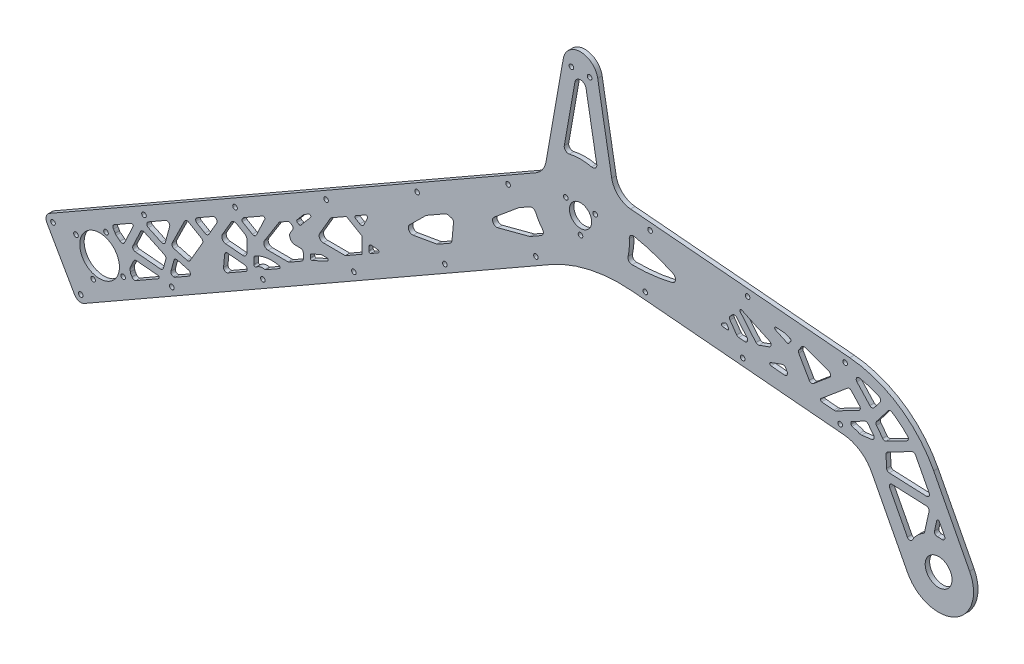
SolidWorks part; units mm, degrees
material "6061-T6 (SS)"
ref_plane "Front Plane" through (0, 0, 0) normal (0, 0, 1) x (1, 0, 0)
ref_plane "Top Plane" through (0, 0, 0) normal (0, 1, 0) x (1, 0, 0)
ref_plane "Right Plane" through (0, 0, 0) normal (1, 0, 0) x (0, 0, -1)
sketch "Reference Sketch" plane through (0, 0, 0) normal (0, 0, 1) x (1, 0, 0)
  line L0 (-343.92, -196.825) -> (0, 0) construction
  line L1 (-243.92, 103.175) -> (356.08, 103.175) construction
  line L2 (-243.92, 103.175) -> (-243.92, 0) construction
  line L3 (-243.92, 0) -> (356.08, 0) construction
  line L4 (356.08, 103.175) -> (356.08, 0) construction
  line L5 (0, 0) -> (256.08, -92.7116) construction
  line L6 (256.08, -92.7116) -> (56.08, -196.825) construction
  line L7 (256.08, -92.7116) -> (456.08, -196.825) construction
  line L8 (-343.92, -196.825) -> (56.08, -196.825) construction
  line L9 (56.08, -196.825) -> (456.08, -196.825) construction
  circle A1 centre (-343.92, -196.825) radius 100 construction
  circle A2 centre (56.08, -196.825) radius 100 construction
  circle A3 centre (456.08, -196.825) radius 100 construction
  circle A4 centre (-343.92, -196.825) radius 16.05 construction
  circle A5 centre (-343.92, -196.825) radius 28.55 construction
  circle A6 centre (-343.92, -196.825) radius 38.55 construction
  circle A7 centre (-343.92, -196.825) radius 33.55 construction
  point P13 (-343.92, -296.825)
  point P14 (556.08, -196.825)
  point P17 (-443.92, -196.825)
  dimension "D3" = 32.1
  dimension "D5" = 200
  dimension "D9" = 57.1
  dimension "D10" = 10
  dimension "D11" = 5
  dimension "D1" = 600
  dimension "D2" = 103.175
  dimension "D4" = 243.92
  dimension "D6" = 125
  dimension "D7" = 400
  dimension "D8" = 1000
  dimension "D12" = 356.08
sketch "Sketch2" plane through (0, 0, 0) normal (0, 0, 1) x (1, 0, 0)
  line L0 (-379.7168, -188.5069) -> (-32.0065, 10.4873)
  line L1 (-354.8814, -231.9028) -> (-21.5627, -41.1449)
  line L2 (-343.92, -196.825) -> (0, 0) construction
  line L3 (-184.3777, -76.7146) -> (-159.5423, -120.1104) construction
  line L4 (-24.685, 20.9013) -> (-12.3101, 91.0831)
  line L5 (12.3101, 91.0831) -> (22.322, 34.3028)
  line L6 (0, 98.4125) -> (0, 112.7) construction
  line L7 (-5.4848, 79.4125) -> (5.4848, 79.4125) construction
  line L8 (5.4848, 79.4125) -> (10.9697, 88.9125) construction
  line L9 (10.9697, 88.9125) -> (5.4848, 98.4125) construction
  line L10 (5.4848, 98.4125) -> (-5.4848, 98.4125) construction
  line L11 (-5.4848, 98.4125) -> (-10.9697, 88.9125) construction
  line L12 (-10.9697, 88.9125) -> (-5.4848, 79.4125) construction
  line L13 (-243.92, 103.175) -> (356.08, 103.175) construction
  line L14 (0, 88.9125) -> (0, 0) construction
  line L15 (35.7868, 21.9646) -> (192.5861, 8.2464)
  line L16 (252.5753, -31.8371) -> (278.2553, -81.1679)
  line L17 (233.9047, -104.2553) -> (208.2247, -54.9245)
  line L18 (36.8237, -28.3172) -> (188.2284, -41.5633)
  line L19 (0, 0) -> (192.5861, -16.8491) construction
  line L21 (-360.8064, -192.2315) -> (-339.3265, -179.9386) construction
  line L22 (-381.5729, -195.33) -> (-361.7045, -230.0467)
  line L23 (256.08, -92.7116) -> (56.08, -196.825) construction
  line L25 (-243.92, 0) -> (356.08, 0) construction
  circle A0 centre (0, 0) radius 7.9375
  circle A1 centre (-343.92, -196.825) radius 14.2
  arc A3 (-12.3101, 91.0831) -> (12.3101, 91.0831) centre (0, 88.9125) cw
  circle A4 centre (0, 88.9125) radius 6.5 construction
  circle A5 centre (-6.5, 88.9125) radius 1.65
  circle A6 centre (6.5, 88.9125) radius 1.65
  circle A7 centre (0, 88.9125) radius 9.5 construction
  arc A8 (252.5753, -31.8371) -> (192.5861, 8.2464) centre (186.0495, -66.4682) ccw
  circle A9 centre (256.08, -92.7116) radius 9.5885
  arc A10 (278.2553, -81.1679) -> (233.9047, -104.2553) centre (256.08, -92.7116) cw
  arc A11 (-21.5627, -41.1449) -> (36.8237, -28.3172) centre (28.1082, -127.9366) cw
  arc A12 (188.2284, -41.5633) -> (208.2247, -54.9245) centre (186.0495, -66.4682) cw
  arc A13 (22.322, 34.3028) -> (35.7868, 21.9646) centre (37.0941, 36.9075) ccw
  arc A14 (-32.0065, 10.4873) -> (-24.685, 20.9013) centre (-39.4572, 23.506) ccw
  circle A17 centre (-343.92, -196.825) radius 17.5 construction
  circle A18 centre (-360.8064, -192.2315) radius 1.65
  circle A19 centre (-339.3265, -179.9386) radius 1.65
  circle A20 centre (-327.0336, -201.4185) radius 1.65
  circle A21 centre (-348.5135, -213.7114) radius 1.65
  arc A27 (-379.7168, -188.5069) -> (-381.5729, -195.33) centre (-377.2333, -192.8465) ccw
  arc A28 (-361.7045, -230.0467) -> (-354.8814, -231.9028) centre (-357.3649, -227.5632) ccw
  circle A29 centre (-343.92, -196.825) radius 33.55 construction
  circle A32 centre (-343.92, -196.825) radius 38.55 construction
  point P16 (-171.96, -98.4125)
  point P64 (-343.92, -196.825)
  dimension "D1" = 15.875
  dimension "D2" = 28.4
  dimension "D3" = 35
  dimension "D5" = 13
  dimension "D6" = 3.3
  dimension "D7" = 6
  dimension "D12" = 50
  dimension "D14" = 100
  dimension "D16" = 15
  dimension "D17" = 5
  dimension "D18" = 25
  dimension "D19" = 3.3
  dimension "D15" = 4
  dimension "D20" = 19.177
  dimension "D4" = 50
  dimension "D8" = 19
  dimension "D9" = 14.2875
  dimension "D10" = 9.525
  dimension "D11" = 10
  dimension "D13" = 50
extrude "Base" add sketch "Sketch2" along normal blind 3.175
sketch "Sketch3" plane through (0, 0, 3.175) normal (0, 0, 1) x (1, 0, 0)
  line L0 (-343.92, -196.825) -> (0, 0) construction
  line L5 (0, 0) -> (197.3986, -17.2701) construction
  line L6 (192.5861, 8.2464) -> (35.7868, 21.9646) construction
  line L9 (36.8237, -28.3172) -> (188.2284, -41.5633) construction
  line L10 (-31.8958, -41.2976) -> (0, 0) construction
  line L11 (0, 0) -> (46.2693, -24.1244) construction
  circle A0 centre (-357.3649, -227.5632) radius 1.65
  circle A1 centre (-343.92, -196.825) radius 33.55 construction
  arc A2 (-361.7045, -230.0467) -> (-354.8814, -231.9028) centre (-357.3649, -227.5632) ccw construction
  circle A3 centre (-292.2711, -190.3101) radius 1.65
  circle A4 centre (-227.1773, -153.057) radius 1.65
  circle A5 centre (-162.0835, -115.8038) radius 1.65
  circle A6 centre (-96.9897, -78.5507) radius 1.65
  circle A7 centre (-31.8958, -41.2976) radius 1.65
  circle A8 centre (-312.1394, -155.5934) radius 1.65
  circle A9 centre (-377.2333, -192.8465) radius 1.65
  circle A10 centre (-247.0456, -118.3403) radius 1.65
  circle A11 centre (-181.9518, -81.0871) radius 1.65
  circle A12 centre (-116.858, -43.834) radius 1.65
  circle A13 centre (-51.7642, -6.5809) radius 1.65
  circle A14 centre (46.2693, -24.1244) radius 1.65
  circle A15 centre (116.0029, -30.2253) radius 1.65
  circle A16 centre (185.7366, -36.3262) radius 1.65
  circle A17 centre (189.2228, 3.5215) radius 1.65
  circle A18 centre (119.4892, 9.6224) radius 1.65
  circle A19 centre (49.7555, 15.7234) radius 1.65
  dimension "D1" = 3.3
  dimension "D2" = 6
  dimension "D3" = 5
  dimension "D5" = 3
  dimension "D4" = 75
  dimension "D6" = 70
extrude "Strut Holes" cut sketch "Sketch3" against normal through all
sketch "Sketch6" plane through (0, 0, 3.175) normal (0, 0, 1) x (1, 0, 0)
  line L0 (-317.9371, -199.2378) -> (-301.7593, -189.9792)
  line L1 (-354.8814, -231.9028) -> (-21.5627, -41.1449) construction
  line L2 (-289.845, -183.1607) -> (-279.9388, -177.4914)
  line L3 (-225.0683, -146.089) -> (-215.3943, -140.5526)
  line L4 (-202.4502, -105.5293) -> (-201.3111, -106.1928)
  line L5 (-333.4446, -172.395) -> (-321.3247, -165.4588)
  line L6 (-32.0065, 10.4873) -> (-379.7168, -188.5069) construction
  line L7 (-319.9233, -166.7528) -> (-326.0767, -179.819)
  line L8 (-329.2222, -183.6702) -> (-327.9453, -183.7868) construction
  line L9 (-302.165, -188.1154) -> (-317.5291, -186.7124)
  line L10 (-319.5204, -187.852) -> (-321.9207, -192.9489)
  line L11 (-296.5261, -175.2812) -> (-298.2962, -181.7883)
  line L12 (-300.4079, -183.2551) -> (-318.4265, -181.6097)
  line L13 (-320.054, -178.7659) -> (-314.5879, -167.159)
  line L14 (-311.9264, -166.2018) -> (-297.6038, -172.9468)
  line L15 (-280.4073, -173.8257) -> (-288.2923, -171.6808)
  line L16 (-290.7472, -173.0857) -> (-292.8686, -180.8843)
  line L17 (-296.7252, -151.3805) -> (-309.1621, -158.4982)
  line L18 (-309.0208, -162.0434) -> (-299.7125, -166.427)
  line L19 (-296.9305, -165.1426) -> (-293.8019, -153.6413)
  line L20 (-290.7492, -165.8308) -> (-281.4187, -168.3689)
  line L21 (-279.1655, -167.4456) -> (-270.335, -152.2839)
  line L22 (-271.0566, -149.5491) -> (-280.339, -144.1428)
  line L23 (-283.1398, -144.9875) -> (-292.0185, -163.0173)
  line L24 (-274.1749, -138.475) -> (-262.8296, -131.9821)
  line L25 (-260.108, -134.7245) -> (-265.8054, -144.5068)
  line L26 (-268.5402, -145.2285) -> (-274.188, -141.9391)
  line L27 (-255.2613, -159.7424) -> (-254.4886, -151.2802)
  line L28 (-252.315, -149.4703) -> (-240.2297, -150.5739)
  line L29 (-292.2711, -190.3101) -> (-299.0066, -188.4038) construction
  line L30 (-252.2762, -161.6601) -> (-239.4181, -154.3014)
  line L31 (-249.9491, -129.2039) -> (-256.1296, -139.8156)
  line L32 (-253.8101, -144.313) -> (-241.8428, -145.4058)
  line L33 (-238.5701, -142.4296) -> (-238.5385, -134.1139)
  line L34 (-240.0286, -131.5101) -> (-245.8469, -128.1214)
  line L35 (-233.5719, -142.9305) -> (-233.588, -147.1604)
  line L36 (-241.7536, -124.7193) -> (-234.6398, -128.8625)
  line L37 (-231.8238, -127.9864) -> (-225.7969, -115.1887)
  line L38 (-227.1983, -113.8948) -> (-240.4869, -121.4998)
  line L39 (-215.7001, -112.1928) -> (-226.033, -128.59)
  line L40 (-223.5063, -133.1894) -> (-209.2023, -133.2437)
  line L41 (-208.2012, -132.9795) -> (-199.2535, -127.8588)
  line L42 (-198.247, -126.1305) -> (-198.2324, -122.2852)
  line L43 (-200.2248, -120.2776) -> (-204.0086, -120.2632)
  line L44 (-207.3776, -114.1307) -> (-205.8611, -111.7242)
  line L45 (-206.5466, -108.9297) -> (-207.4931, -108.3784)
  line L46 (-209.4931, -108.3708) -> (-215.0015, -111.5233)
  line L47 (-220.5938, -138.2005) -> (-191.3457, -138.3115) construction
  line L48 (-200.0442, -105.9743) -> (-193.1087, -97.7724)
  line L49 (-194.3691, -96.2588) -> (-197.5103, -98.0565)
  line L50 (-198.0441, -98.501) -> (-202.7105, -104.0195)
  line L51 (-193.2277, -121.0545) -> (-193.2345, -122.8478)
  line L52 (-191.8153, -123.7595) -> (-180.9934, -118.7631)
  line L54 (-192.6468, -120.1504) -> (-185.8787, -117.0256)
  line L55 (-185.0328, -116.8414) -> (-181.4088, -116.8552)
  line L56 (-168.149, -108.9055) -> (-183.9527, -108.8455)
  line L57 (-186.5337, -104.3356) -> (-178.5799, -90.6792)
  line L58 (-178.5799, -90.6792) -> (-167.3868, -84.2735)
  line L59 (-167.3868, -84.2735) -> (-156.3884, -90.6792)
  line L60 (-156.3884, -90.6792) -> (-156.4321, -102.1999)
  line L61 (-156.4321, -102.1999) -> (-168.149, -108.9055)
  line L62 (-178.5799, -90.6792) -> (-168.149, -108.9055) construction
  line L63 (-151.4146, -97.6001) -> (-151.4054, -95.1814)
  line L64 (-149.2236, -93.1973) -> (-145.0326, -93.58)
  line L65 (-144.6268, -95.4437) -> (-149.9179, -98.4719)
  line L66 (-160.8726, -80.5454) -> (-153.7619, -76.4759)
  line L67 (-152.3605, -77.7699) -> (-154.93, -83.2262)
  line L68 (-157.746, -84.1023) -> (-160.8792, -82.2774)
  line L69 (-155.8599, -85.2008) -> (-151.3971, -92.9988) construction
  line L70 (-90.8199, -49.6985) -> (-91.8964, -61.4879)
  line L71 (-93.3939, -63.8188) -> (-101.9943, -68.7409)
  line L72 (-102.9747, -69.0935) -> (-119.6299, -71.9651)
  line L73 (-122.2529, -66.8794) -> (-110.6811, -55.3952)
  line L74 (-110.058, -54.9208) -> (-96.7247, -47.2901)
  line L75 (-94.4471, -46.9991) -> (-92.2866, -47.5868)
  line L76 (-102.4534, -69.0036) -> (-110.4008, -55.117) construction
  line L78 (-28.0968, -26.4494) -> (-35.8254, -30.8725)
  line L79 (-36.5501, -31.1694) -> (-59.134, -37.129)
  line L80 (-61.819, -31.9228) -> (-44.3172, -17.3499)
  line L81 (-43.8877, -17.0516) -> (-36.2746, -12.6946)
  line L82 (-44.1155, -17.182) -> (-36.1682, -31.0687) construction
  line L83 (-11.5997, 37.5245) -> (-3.9861, 80.7029)
  line L84 (3.9861, 80.7029) -> (11.5997, 37.5245)
  line L85 (22.322, 34.3028) -> (12.3101, 91.0831) construction
  line L86 (-12.3101, 91.0831) -> (-24.685, 20.9013) construction
  line L87 (192.5861, 8.2464) -> (35.7868, 21.9646) construction
  line L88 (36.8237, -28.3172) -> (188.2284, -41.5633) construction
  line L89 (-227.1773, -153.057) -> (-233.9128, -151.1507) construction
  line L90 (246.076, -72.9136) -> (249.254, -58.5784)
  line L91 (247.3887, -56.1475) -> (222.9622, -55.081)
  line L92 (221.1009, -58.0026) -> (233.7353, -82.273)
  line L93 (208.2247, -54.9245) -> (233.9047, -104.2553) construction
  line L94 (253.1337, -68.7997) -> (254.752, -61.5)
  line L95 (256.6153, -61.2547) -> (260.3456, -68.4206)
  line L96 (278.2553, -81.1679) -> (252.5753, -31.8371) construction
  line L97 (249.3108, -47.2228) -> (239.5975, -28.5637)
  line L98 (236.9, -27.7132) -> (219.5656, -36.7369)
  line L99 (218.491, -38.5982) -> (218.8608, -47.0688)
  line L100 (220.7717, -48.9796) -> (247.4495, -50.1444)
  line L101 (233.4135, -22.7639) -> (218.6181, -30.4658)
  line L102 (216.1079, -29.9093) -> (211.6718, -24.1281)
  line L103 (211.6718, -21.693) -> (220.0072, -10.8302)
  line L104 (209.6166, -31.3057) -> (205.7463, -26.2618)
  line L105 (203.2361, -25.7053) -> (194.0101, -30.5081)
  line L106 (193.4718, -31.3951) -> (193.4718, -32.4967)
  line L107 (201.069, -35.4569) -> (208.2909, -34.5061)
  line L108 (214.3031, -8.4078) -> (209.9577, -14.0708)
  line L109 (197.6887, -4.156) -> (206.8964, -14.2045)
  line L110 (193.6814, -11.6243) -> (199.5455, -18.0239)
  line L111 (198.9945, -21.1491) -> (182.8075, -29.5754)
  line L112 (181.1608, -29.903) -> (172.4826, -29.1438)
  line L113 (171.927, -27.3815) -> (190.9213, -11.4434)
  line L114 (178.1992, -11.0225) -> (166.5918, -20.7623)
  line L115 (163.5742, -20.2302) -> (156.048, -7.1944)
  line L116 (156.1417, -5.0472) -> (158.1885, -2.1242)
  line L117 (160.5108, -1.3919) -> (177.5977, -7.611)
  line L118 (146.6448, -20.9077) -> (147.747, -22.8167)
  line L119 (145.8406, -25.8091) -> (136.23, -24.9682)
  line L120 (135.9751, -23.0324) -> (144.2287, -20.0283)
  line L121 (134.9743, -13.819) -> (127.6718, -16.4769)
  line L122 (125.4557, -15.8831) -> (114.1985, -2.4673)
  line L123 (115.3872, -0.9182) -> (135.1355, -10.127)
  line L124 (139.4306, -1.096) -> (147.8318, -5.0136)
  line L125 (149.0736, -4.6809) -> (150.4259, -2.7496)
  line L126 (149.9488, -1.2363) -> (146.0985, 0.1651)
  line L127 (145.3339, 0.3346) -> (139.9404, 0.8065)
  line L128 (111.6605, -7.2212) -> (119.0455, -16.0223)
  line L129 (117.3391, -19.3002) -> (113.1162, -18.9308)
  line L130 (111.6522, -18.0855) -> (106.8775, -11.2665)
  line L131 (107.1016, -8.7052) -> (108.7142, -7.0926)
  line L132 (104.7039, -15.1361) -> (105.7554, -16.6377)
  line L133 (104.8491, -18.2075) -> (101.6773, -17.93)
  line L134 (101.2644, -16.0678) -> (103.3847, -14.8436)
  arc A0 (-320.7312, -198.3723) -> (-321.5152, -197.1118) centre (-327.0336, -201.4185) ccw
  arc A1 (-291.1568, -183.3993) -> (-291.2348, -183.3872) centre (-292.2711, -190.3101) ccw
  arc A2 (-225.7665, -146.2006) -> (-231.9116, -147.9008) centre (-227.1773, -153.057) ccw
  arc A4 (-321.937, -195.96) -> (-322.0953, -194.053) centre (-343.92, -196.825) ccw
  arc A5 (-332.8179, -177.3623) -> (-333.9791, -175.4215) centre (-339.3265, -179.9386) ccw
  arc A6 (-329.2222, -180.455) -> (-332.0384, -178.3094) centre (-343.92, -196.825) ccw
  arc A8 (-232.5183, -141.1762) -> (-215.6911, -138.7049) centre (-220.6887, -163.2003) cw
  arc A9 (-241.9747, -123.1658) -> (-241.1717, -122.1478) centre (-247.0456, -118.3403) ccw
  arc A10 (-32.0383, -14.0906) -> (-27.2511, -21.9631) centre (0, 0) ccw
  arc A11 (-256.1296, -139.8156) -> (-253.8101, -144.313) centre (-253.5373, -141.3254) ccw
  arc A12 (-226.033, -128.59) -> (-223.5063, -133.1894) centre (-223.4949, -130.1894) ccw
  arc A13 (-183.9527, -108.8455) -> (-186.5337, -104.3356) centre (-183.9413, -105.8455) cw
  arc A14 (-119.6299, -71.9651) -> (-122.2529, -66.8794) centre (-120.1396, -69.0087) cw
  arc A15 (-59.134, -37.129) -> (-61.819, -31.9228) centre (-59.8994, -34.2283) cw
  arc A16 (-7.9627, 34.0822) -> (7.9627, 34.0822) centre (0, 0) cw
  arc A17 (-3.9861, 80.7029) -> (3.9861, 80.7029) centre (0, 80) cw
  arc A18 (34.8636, 3.0867) -> (34.0029, -8.2948) centre (0, 0) cw
  arc A19 (38.4335, 6.2944) -> (66.0977, -2.7713) centre (15.1723, -111.4295) cw
  arc A20 (66.0977, -2.7713) -> (65.4856, -8.7407) centre (64.749, -5.6491) cw
  arc A21 (36.898, -12.0057) -> (65.4856, -8.7407) centre (37.6733, 107.9918) ccw
  arc A22 (245.141, -74.2025) -> (237.26, -82.3165) centre (256.08, -92.7116) ccw
  arc A23 (258.3595, -71.3328) -> (255.1708, -71.2308) centre (256.08, -92.7116) ccw
  arc A24 (222.6875, -10.3732) -> (233.9189, -19.5905) centre (186.0495, -66.4682) cw
  arc A25 (252.5753, -31.8371) -> (192.5861, 8.2464) centre (186.0495, -66.4682) ccw construction
  arc A26 (194.2312, -33.4673) -> (199.4914, -35.2382) centre (186.0495, -66.4682) cw
  arc A27 (208.2247, -54.9245) -> (188.2284, -41.5633) centre (186.0495, -66.4682) ccw construction
  arc A28 (213.5369, -5.3663) -> (199.5667, -0.8459) centre (186.0495, -66.4682) ccw
  arc A29 (218.8608, -47.0688) -> (220.7717, -48.9796) centre (220.8589, -46.9815) ccw
  arc A30 (239.5975, -28.5637) -> (236.9, -27.7132) centre (237.8235, -29.4872) ccw
  arc A31 (219.5656, -36.7369) -> (218.491, -38.5982) centre (220.4891, -38.5109) ccw
  arc A32 (127.6718, -16.4769) -> (125.4557, -15.8831) centre (126.9878, -14.5975) cw
  arc A33 (-240.4869, -121.4998) -> (-241.1717, -122.1478) centre (-239.4934, -123.2356) ccw
  arc A34 (-234.6398, -128.8625) -> (-231.8238, -127.9864) centre (-233.6332, -127.1343) ccw
  arc A35 (-233.5719, -142.9305) -> (-232.5183, -141.1762) centre (-231.5719, -142.9381) cw
  arc A36 (-317.9371, -199.2378) -> (-320.7312, -198.3723) centre (-318.9305, -197.5019) cw
  arc A37 (-321.937, -195.96) -> (-321.5152, -197.1118) centre (-319.9386, -195.8813) ccw
  arc A38 (-321.9207, -192.9489) -> (-322.0953, -194.053) centre (-320.1113, -193.801) ccw
  arc A39 (-317.5291, -186.7124) -> (-319.5204, -187.852) centre (-317.711, -188.7042) ccw
  arc A42 (-332.8179, -177.3623) -> (-332.0384, -178.3094) centre (-330.9583, -176.6261) ccw
  arc A43 (-333.4446, -172.395) -> (-333.9791, -175.4215) centre (-332.4512, -174.1309) ccw
  arc A44 (-318.4265, -181.6097) -> (-320.054, -178.7659) centre (-318.2446, -179.618) cw
  arc A45 (-298.2962, -181.7883) -> (-300.4079, -183.2551) centre (-300.226, -181.2634) cw
  arc A46 (-289.845, -183.1607) -> (-291.1568, -183.3993) centre (-290.8384, -181.4248) cw
  arc A47 (-292.8686, -180.8843) -> (-291.2348, -183.3872) centre (-290.9387, -181.4092) ccw
  arc A48 (-280.4073, -173.8257) -> (-279.9388, -177.4914) centre (-280.9322, -175.7556) cw
  arc A49 (-288.2923, -171.6808) -> (-290.7472, -173.0857) centre (-288.8173, -173.6107) ccw
  arc A50 (-296.5261, -175.2812) -> (-297.6038, -172.9468) centre (-298.456, -174.7562) ccw
  arc A51 (-314.5879, -167.159) -> (-311.9264, -166.2018) centre (-312.7785, -168.0112) cw
  arc A52 (-309.1621, -158.4982) -> (-309.0208, -162.0434) centre (-308.1687, -160.234) ccw
  arc A53 (-296.7252, -151.3805) -> (-293.8019, -153.6413) centre (-295.7318, -153.1164) cw
  arc A54 (-299.7125, -166.427) -> (-296.9305, -165.1426) centre (-298.8604, -164.6177) ccw
  arc A55 (-290.7492, -165.8308) -> (-292.0185, -163.0173) centre (-290.2242, -163.9009) cw
  arc A56 (-281.4187, -168.3689) -> (-279.1655, -167.4456) centre (-280.8937, -166.439) ccw
  arc A57 (-270.335, -152.2839) -> (-271.0566, -149.5491) centre (-272.0632, -151.2774) ccw
  arc A58 (-280.339, -144.1428) -> (-283.1398, -144.9875) centre (-281.3456, -145.8711) ccw
  arc A59 (-274.1749, -138.475) -> (-274.188, -141.9391) centre (-273.1814, -140.2108) ccw
  arc A60 (-265.8054, -144.5068) -> (-268.5402, -145.2285) centre (-267.5336, -143.5003) cw
  arc A61 (-254.4886, -151.2802) -> (-252.315, -149.4703) centre (-252.4969, -151.462) cw
  arc A62 (-255.2613, -159.7424) -> (-252.2762, -161.6601) centre (-253.2696, -159.9243) ccw
  arc A63 (-239.4181, -154.3014) -> (-240.2297, -150.5739) centre (-240.4115, -152.5656) ccw
  arc A64 (-262.8296, -131.9821) -> (-260.108, -134.7245) centre (-261.8362, -133.718) cw
  arc A65 (-209.2023, -133.2437) -> (-208.2012, -132.9795) centre (-209.1947, -131.2437) ccw
  arc A66 (-215.0015, -111.5233) -> (-215.7001, -112.1928) centre (-214.0081, -113.2591) ccw
  arc A67 (-207.4931, -108.3784) -> (-209.4931, -108.3708) centre (-208.4997, -110.1067) ccw
  arc A68 (-205.8611, -111.7242) -> (-206.5466, -108.9297) centre (-207.5531, -110.658) ccw
  arc A69 (-204.0086, -120.2632) -> (-207.3776, -114.1307) centre (-203.9934, -116.2633) cw
  arc A70 (-198.2324, -122.2852) -> (-200.2248, -120.2776) centre (-200.2323, -122.2776) ccw
  arc A71 (-199.2535, -127.8588) -> (-198.247, -126.1305) centre (-200.2469, -126.1229) ccw
  arc A72 (-185.8787, -117.0256) -> (-185.0328, -116.8414) centre (-185.0404, -118.8414) cw
  arc A73 (-197.5103, -98.0565) -> (-198.0441, -98.501) centre (-196.5169, -99.7924) ccw
  arc A74 (-151.4054, -95.1814) -> (-149.2236, -93.1973) centre (-149.4054, -95.189) cw
  arc A75 (-154.93, -83.2262) -> (-157.746, -84.1023) centre (-156.7394, -82.374) cw
  arc A76 (-90.8199, -49.6985) -> (-92.2866, -47.5868) centre (-92.8116, -49.5167) ccw
  arc A77 (111.6605, -7.2212) -> (108.7142, -7.0926) centre (110.1284, -8.5068) ccw
  arc A78 (106.8775, -11.2665) -> (107.1016, -8.7052) centre (108.5158, -10.1194) cw
  arc A79 (113.1162, -18.9308) -> (111.6522, -18.0855) centre (113.2905, -16.9384) cw
  arc A80 (119.0455, -16.0223) -> (117.3391, -19.3002) centre (117.5134, -17.3078) cw
  arc A81 (134.9743, -13.819) -> (135.1355, -10.127) centre (134.2903, -11.9396) ccw
  arc A82 (146.6448, -20.9077) -> (144.2287, -20.0283) centre (144.9128, -21.9077) ccw
  arc A83 (147.747, -22.8167) -> (145.8406, -25.8091) centre (146.0149, -23.8167) cw
  arc A84 (156.048, -7.1944) -> (156.1417, -5.0472) centre (157.78, -6.1944) cw
  arc A85 (158.1885, -2.1242) -> (160.5108, -1.3919) centre (159.8268, -3.2713) cw
  arc A86 (178.1992, -11.0225) -> (177.5977, -7.611) centre (176.9136, -9.4904) ccw
  arc A87 (166.5918, -20.7623) -> (163.5742, -20.2302) centre (165.3062, -19.2302) cw
  arc A88 (193.6814, -11.6243) -> (190.9213, -11.4434) centre (192.2068, -12.9755) ccw
  arc A89 (199.5455, -18.0239) -> (198.9945, -21.1491) centre (198.071, -19.375) cw
  arc A90 (209.9577, -14.0708) -> (206.8964, -14.2045) centre (208.371, -12.8533) cw
  arc A91 (213.5369, -5.3663) -> (214.3031, -8.4078) centre (212.7164, -7.1903) cw
  arc A92 (233.9189, -19.5905) -> (233.4135, -22.7639) centre (232.49, -20.9899) cw
  arc A93 (222.6875, -10.3732) -> (220.0072, -10.8302) centre (221.5939, -12.0477) ccw
  arc A94 (211.6718, -24.1281) -> (211.6718, -21.693) centre (213.2585, -22.9105) cw
  arc A95 (218.6181, -30.4658) -> (216.1079, -29.9093) centre (217.6946, -28.6918) cw
  arc A96 (205.7463, -26.2618) -> (203.2361, -25.7053) centre (204.1595, -27.4793) ccw
  arc A97 (209.6166, -31.3057) -> (208.2909, -34.5061) centre (208.0299, -32.5232) cw
  arc A98 (246.076, -72.9136) -> (245.141, -74.2025) centre (244.1234, -72.4807) cw
  arc A99 (249.254, -58.5784) -> (247.3887, -56.1475) centre (247.3014, -58.1456) ccw
  arc A100 (222.9622, -55.081) -> (221.1009, -58.0026) centre (222.8749, -57.0791) ccw
  arc A101 (233.7353, -82.273) -> (237.26, -82.3165) centre (235.5093, -81.3495) ccw
  arc A102 (260.3456, -68.4206) -> (258.3595, -71.3328) centre (258.5716, -69.344) cw
  arc A103 (253.1337, -68.7997) -> (255.1708, -71.2308) centre (255.0863, -69.2326) ccw
  arc A104 (249.3108, -47.2228) -> (247.4495, -50.1444) centre (247.5367, -48.1463) cw
  arc A105 (199.5667, -0.8459) -> (197.6887, -4.156) centre (199.1632, -2.8048) ccw
  arc A106 (-215.6911, -138.7049) -> (-215.3943, -140.5526) centre (-215.891, -139.6847) cw
  arc A107 (-301.7593, -189.9792) -> (-302.165, -188.1154) centre (-302.256, -189.1113) ccw
  arc A108 (-321.3247, -165.4588) -> (-319.9233, -166.7528) centre (-320.828, -166.3267) cw
  arc A109 (-225.7969, -115.1887) -> (-227.1983, -113.8948) centre (-226.7016, -114.7627) ccw
  arc A110 (-241.7536, -124.7193) -> (-241.9747, -123.1658) centre (-241.2503, -123.8551) cw
  arc A111 (-225.7665, -146.2006) -> (-225.0683, -146.089) centre (-225.565, -145.2211) ccw
  arc A112 (-233.588, -147.1604) -> (-231.9116, -147.9008) centre (-232.588, -147.1642) ccw
  arc A113 (-202.4502, -105.5293) -> (-202.7105, -104.0195) centre (-201.9469, -104.6652) cw
  arc A114 (-201.3111, -106.1928) -> (-200.0442, -105.9743) centre (-200.8078, -105.3286) ccw
  arc A115 (-193.2277, -121.0545) -> (-192.6468, -120.1504) centre (-192.2277, -121.0583) cw
  arc A116 (-193.2345, -122.8478) -> (-191.8153, -123.7595) centre (-192.2345, -122.8516) ccw
  arc A117 (-193.1087, -97.7724) -> (-194.3691, -96.2588) centre (-193.8723, -97.1267) ccw
  arc A118 (-180.9934, -118.7631) -> (-181.4088, -116.8552) centre (-181.4126, -117.8552) ccw
  arc A119 (-153.7619, -76.4759) -> (-152.3605, -77.7699) centre (-153.2652, -77.3438) cw
  arc A120 (-160.8726, -80.5454) -> (-160.8792, -82.2774) centre (-160.3759, -81.4133) ccw
  arc A121 (-151.4146, -97.6001) -> (-149.9179, -98.4719) centre (-150.4146, -97.6039) ccw
  arc A122 (-145.0326, -93.58) -> (-144.6268, -95.4437) centre (-145.1235, -94.5758) cw
  arc A123 (101.6773, -17.93) -> (101.2644, -16.0678) centre (101.7644, -16.9338) cw
  arc A124 (104.7039, -15.1361) -> (103.3847, -14.8436) centre (103.8847, -15.7096) ccw
  arc A125 (105.7554, -16.6377) -> (104.8491, -18.2075) centre (104.9362, -17.2113) cw
  arc A126 (114.1985, -2.4673) -> (115.3872, -0.9182) centre (114.9646, -1.8245) cw
  arc A127 (136.23, -24.9682) -> (135.9751, -23.0324) centre (136.3171, -23.972) cw
  arc A128 (139.4306, -1.096) -> (139.9404, 0.8065) centre (139.8532, -0.1897) cw
  arc A129 (172.4826, -29.1438) -> (171.927, -27.3815) centre (172.5698, -28.1476) cw
  arc A130 (194.0101, -30.5081) -> (193.4718, -31.3951) centre (194.4718, -31.3951) ccw
  arc A131 (193.4718, -32.4967) -> (194.2312, -33.4673) centre (194.4718, -32.4967) ccw
  arc A132 (254.752, -61.5) -> (256.6153, -61.2547) centre (255.7283, -61.7164) cw
  arc A133 (146.0985, 0.1651) -> (145.3339, 0.3346) centre (145.0724, -2.654) ccw
  arc A134 (199.4914, -35.2382) -> (201.069, -35.4569) centre (200.6774, -32.4826) ccw
  arc A135 (182.8075, -29.5754) -> (181.1608, -29.903) centre (181.4223, -26.9144) cw
  arc A136 (-7.9627, 34.0822) -> (-11.5997, 37.5245) centre (-8.6452, 37.0035) cw
  arc A137 (7.9627, 34.0822) -> (11.5997, 37.5245) centre (8.6452, 37.0035) ccw
  arc A138 (34.8636, 3.0867) -> (38.4335, 6.2944) centre (37.8519, 3.3513) cw
  arc A139 (34.0029, -8.2948) -> (36.898, -12.0057) centre (36.9174, -9.0058) ccw
  arc A140 (-35.8254, -30.8725) -> (-36.5501, -31.1694) centre (-37.3155, -28.2687) cw
  arc A141 (-44.3172, -17.3499) -> (-43.8877, -17.0516) centre (-42.3976, -19.6554) cw
  arc A142 (-32.0383, -14.0906) -> (-36.2746, -12.6946) centre (-34.7845, -15.2984) ccw
  arc A143 (-27.2511, -21.9631) -> (-28.0968, -26.4494) centre (-29.5869, -23.8456) cw
  arc A144 (-96.7247, -47.2901) -> (-94.4471, -46.9991) centre (-95.2346, -49.8939) cw
  arc A145 (-91.8964, -61.4879) -> (-93.3939, -63.8188) centre (-94.884, -61.2151) cw
  arc A146 (-110.6811, -55.3952) -> (-110.058, -54.9208) centre (-108.5679, -57.5245) cw
  arc A147 (-101.9943, -68.7409) -> (-102.9747, -69.0935) centre (-103.4845, -66.1371) cw
  arc A148 (-249.9491, -129.2039) -> (-245.8469, -128.1214) centre (-247.3568, -130.7138) cw
  arc A149 (-238.5385, -134.1139) -> (-240.0286, -131.5101) centre (-241.5385, -134.1025) ccw
  arc A150 (-241.8428, -145.4058) -> (-238.5701, -142.4296) centre (-241.57, -142.4182) ccw
  arc A151 (150.4259, -2.7496) -> (149.9488, -1.2363) centre (149.6067, -2.176) ccw
  arc A152 (147.8318, -5.0136) -> (149.0736, -4.6809) centre (148.2544, -4.1073) ccw
  arc A153 (-329.2222, -180.455) -> (-326.0767, -179.819) centre (-327.8861, -178.9669) ccw
  point P98 (-116.858, -43.834)
  point P110 (-258.4996, -143.8848)
  point P113 (-228.9184, -133.1688)
  point P143 (34.9003, -2.6394)
  point P203 (218.9408, -48.8997)
  point P206 (238.674, -26.7897)
  point P211 (126.3559, -16.9559)
  point P214 (-240.9361, -121.7569)
  point P217 (-232.7537, -129.961)
  point P220 (-233.5675, -141.7728)
  point P229 (-318.9237, -186.5851)
  point P232 (-327.9453, -183.7868)
  point P235 (-326.0754, -183.9575)
  point P240 (-335.9304, -173.8176)
  point P247 (-290.5028, -183.5371)
  point P252 (-275.7482, -175.0931)
  point P255 (-290.2222, -171.1558)
  point P262 (-312.4966, -160.4065)
  point P265 (-292.5345, -148.9822)
  point P268 (-297.5562, -167.4426)
  point P271 (-293.0903, -165.1939)
  point P278 (-282.1923, -143.0634)
  point P281 (-277.1814, -140.1957)
  point P288 (-255.6107, -163.5684)
  point P294 (-256.3514, -128.2747)
  point P297 (-208.6664, -133.2457)
  point P300 (-215.4343, -111.7709)
  point P303 (-208.4909, -107.7973)
  point P308 (-211.2248, -120.2358)
  point P311 (-198.2248, -120.2852)
  point P314 (-198.2513, -127.2852)
  point P329 (110.2575, -5.5492)
  point P334 (112.1872, -18.8495)
  point P337 (122.1491, -19.721)
  point P340 (139.5116, -12.1676)
  point P345 (149.6679, -26.1439)
  point P350 (159.0687, -0.8671)
  point P353 (180.8529, -8.7958)
  point P356 (164.7659, -22.2944)
  point P363 (208.5067, -15.9618)
  point P366 (215.8118, -6.4415)
  point P369 (235.7568, -21.544)
  point P374 (210.7376, -22.9105)
  point P377 (217.1296, -31.2407)
  point P380 (204.7246, -24.9304)
  point P383 (211.7254, -34.054)
  point P390 (219.5014, -54.9299)
  point P393 (235.6626, -85.9753)
  point P396 (262.2729, -72.1228)
  point P401 (250.9103, -50.2955)
  point P406 (-213.2581, -139.3301)
  point P412 (-318.5721, -163.8835)
  point P415 (-224.4456, -112.3194)
  point P420 (-225.4089, -146.284)
  point P423 (-233.5998, -150.2728)
  point P426 (-203.48, -104.9295)
  point P431 (-193.2252, -120.4175)
  point P434 (-193.2404, -124.4175)
  point P437 (-189.4469, -93.4418)
  point P440 (-176.8981, -116.8723)
  point P447 (-151.4212, -99.3322)
  point P450 (-141.8741, -93.8684)
  point P453 (98.5177, -17.6536)
  point P458 (106.9854, -18.3944)
  point P463 (131.7364, -24.5751)
  point P468 (170.0776, -28.9333)
  point P471 (193.4718, -30.7883)
  point P474 (193.4718, -33.2883)
  point P477 (255.3467, -58.8176)
  point P484 (182.0319, -29.9792)
  point P491 (34.2849, 7.0387)
  point P494 (32.91, -11.9136)
  point P505 (-24.8853, -24.6115)
  point P508 (-95.6462, -46.6729)
  point P511 (-92.0384, -63.0431)
  point P524 (-238.5825, -145.7035)
  point P527 (151.1734, -1.682)
  point P530 (148.5923, -5.3682)
  dimension "D1" = 14
  dimension "D2" = 10
  dimension "D3" = 2
  dimension "D5" = 22
  dimension "D6" = 9
  dimension "D12" = 5
  dimension "D19" = 7
  dimension "D31" = 7
  dimension "D40" = 25
  dimension "D44" = 19
  dimension "D62" = 5
  dimension "D92" = 35
  dimension "D96" = 3
  dimension "D97" = 10
  dimension "D100" = 15
  dimension "D104" = 30
  dimension "D105" = 120
  dimension "D107" = 43
  dimension "D116" = 65
  dimension "D117" = 8
  dimension "D127" = 9
  dimension "D128" = 6
  dimension "D171" = 2
  dimension "D172" = 1
  dimension "D173" = 3
  dimension "D174" = 1
  dimension "D175" = 4
  dimension "D176" = 2
  dimension "D7" = 35
  dimension "D8" = 35
  dimension "D9" = 20
  dimension "D10" = 22
  dimension "D11" = 20
  dimension "D13" = 5
  dimension "D14" = 45
  dimension "D15" = 45
  dimension "D16" = 17
  dimension "D17" = 15
  dimension "D18" = 5
  dimension "D20" = 55
  dimension "D21" = 5
  dimension "D22" = 45
  dimension "D23" = 23
  dimension "D24" = 34
  dimension "D25" = 60
  dimension "D26" = 5
  dimension "D27" = 5
  dimension "D28" = 5
  dimension "D29" = 30
  dimension "D30" = 24
  dimension "D32" = 55
  dimension "D33" = 35
  dimension "D34" = 25
  dimension "D35" = 5
  dimension "D36" = 6
  dimension "D37" = 60
  dimension "D38" = 5
  dimension "D39" = 20
  dimension "D41" = 11
  dimension "D42" = 35
  dimension "D43" = 60
  dimension "D45" = 19.5
  dimension "D46" = 5
  dimension "D47" = 5
  dimension "D48" = 30
  dimension "D49" = 5
  dimension "D50" = 14
  dimension "D51" = 13
  dimension "D52" = 8.5
  dimension "D53" = 60
  dimension "D54" = 12
  dimension "D55" = 7
  dimension "D56" = 22
  dimension "D57" = 28
  dimension "D58" = 60
  dimension "D59" = 15
  dimension "D60" = 8
  dimension "D61" = 13
  dimension "D63" = 12
  dimension "D64" = 20
  dimension "D65" = 5
  dimension "D66" = 65
  dimension "D67" = 25
  dimension "2" = 18
  dimension "D68" = 8
  dimension "D69" = 4
  dimension "D70" = 14
  dimension "D71" = 15
  dimension "D72" = 13.5
  dimension "D73" = 60
  dimension "D74" = 60
  dimension "D75" = 8
  dimension "D76" = 5
  dimension "D77" = 35
  dimension "D78" = 0.5076
  dimension "D79" = 5
  dimension "D80" = 11
  dimension "D81" = 35
  dimension "D82" = 16
  dimension "D83" = 18
  dimension "D84" = 55
  dimension "D85" = 45
  dimension "D86" = 20
  dimension "D87" = 15
  dimension "D88" = 12
  dimension "D89" = 17
  dimension "D90" = 16
  dimension "D91" = 18
  dimension "D93" = 15
  dimension "D94" = 10
  dimension "D95" = 13
  dimension "D98" = 10
  dimension "D99" = 80
  dimension "D101" = 16
  dimension "D102" = 22
  dimension "D103" = 22
  dimension "D106" = 7
  dimension "D108" = 10
  dimension "D109" = 40
  dimension "D110" = 10
  dimension "D111" = 6
  dimension "D112" = 60
  dimension "D113" = 35
  dimension "D114" = 15
  dimension "D115" = 6
  dimension "D118" = 26.5
  dimension "D119" = 6
  dimension "D120" = 85
  dimension "D121" = 85
  dimension "D122" = 32
  dimension "D123" = 21
  dimension "D124" = 80
  dimension "D125" = 75
  dimension "D126" = 6
  dimension "D129" = 10.5
  dimension "D130" = 80
  dimension "D131" = 12
  dimension "D132" = 8
  dimension "D133" = 6
  dimension "D134" = 2.5
  dimension "D135" = 100
  dimension "D136" = 11.5
  dimension "D137" = 60
  dimension "D138" = 11
  dimension "D139" = 45
  dimension "D140" = 12
  dimension "D141" = 8.5
  dimension "D142" = 12
  dimension "D143" = 18
  dimension "D144" = 80
  dimension "D145" = 21
  dimension "D146" = 60
  dimension "D147" = 60
  dimension "D148" = 15
  dimension "D149" = 12
  dimension "D150" = 18
  dimension "D151" = 25
  dimension "D152" = 9
  dimension "D153" = 12
  dimension "D154" = 6
  dimension "D155" = 15
  dimension "D156" = 20
  dimension "D157" = 10
  dimension "D158" = 13.5
  dimension "D159" = 4.5
  dimension "D160" = 45
  dimension "D161" = 14
  dimension "D162" = 5
  dimension "D163" = 10
  dimension "D164" = 16
  dimension "D165" = 50
  dimension "D166" = 18.5
  dimension "D167" = 50
  dimension "D168" = 4
  dimension "D169" = 8.5
  dimension "D170" = 35
extrude "Lightening Holes" cut sketch "Sketch6" against normal through all
sketch "Sketch7" plane through (0, 0, 3.175) normal (0, 0, 1) x (1, 0, 0)
  circle A0 centre (-10.5, 6.0622) radius 1.65
  circle A1 centre (10.5, 6.0622) radius 1.65
  circle A2 centre (0, -12.1244) radius 1.65
  point P8 (0, 0)
  dimension "D1" = 3.3
  dimension "D3" = 21
  dimension "D2" = 3
extrude "Cut-Extrude1" cut sketch "Sketch7" against normal through all
